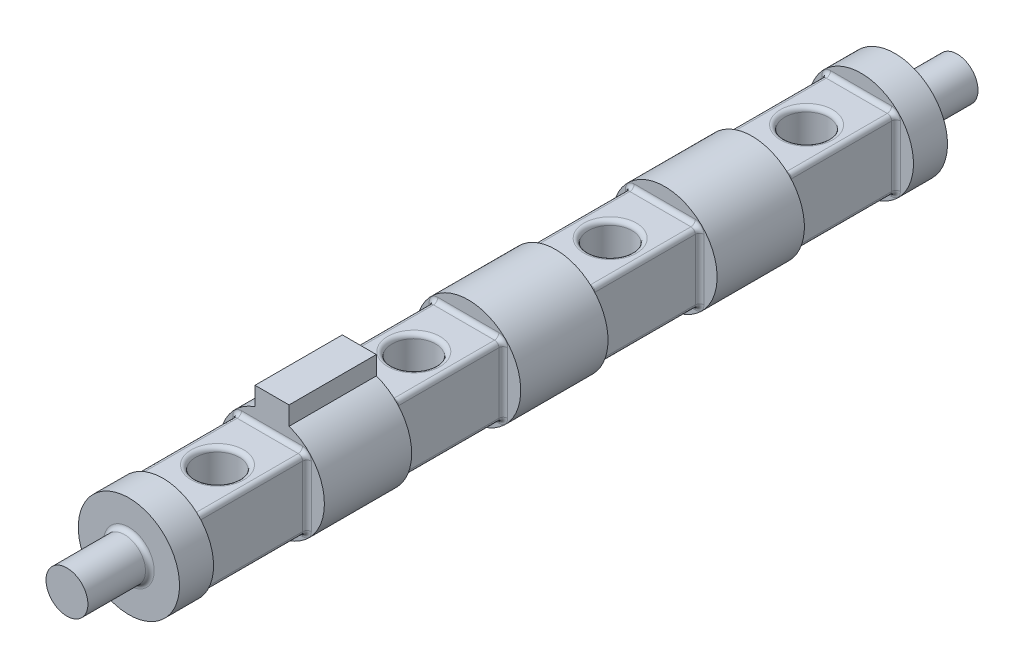
SolidWorks part; units mm, degrees
ref_plane "Front Plane" through (0, 0, 0) normal (0, 0, 1) x (1, 0, 0)
ref_plane "Top Plane" through (0, 0, 0) normal (0, 1, 0) x (1, 0, 0)
ref_plane "Right Plane" through (0, 0, 0) normal (1, 0, 0) x (0, 0, -1)
sketch "Sketch1" plane through (0, 0, 0) normal (0, 0, 1) x (1, 0, 0)
  circle A0 centre (0, 0) radius 6
  dimension "D3" = 12
extrude "Boss-Extrude1" add sketch "Sketch1" along normal blind 100
ref_plane "Midplane" through (0, 0, 50) normal (0, 0, -1) x (-1, 0, 0)
sketch "Sketch2" plane through (0, 0, 50) normal (0, 0, -1) x (-1, 0, 0)
  circle A2 centre (0, 0) radius 2.4
  dimension "D1" = 4.8
extrude "Boss-Extrude2" add sketch "Sketch2" along normal mid plane 102
sketch "Sketch3" plane through (0, 0, 0) normal (0, 0, -1) x (-1, 0, 0)
  line L1 (-4, -4) -> (4, -4)
  line L2 (-4, -4) -> (-4, 4)
  line L3 (-4, 4) -> (4, 4)
  line L4 (4, -4) -> (4, 4)
  line L5 (-4, -4) -> (4, 4) construction
  line L6 (-4, 4) -> (4, -4) construction
  circle A0 centre (0, 0) radius 6 construction
  circle A1 centre (0, 0) radius 6
  dimension "D1" = 8
  dimension "D2" = 8
extrude "Cut-Extrude1" cut sketch "Sketch3" against normal blind 12.5 from offset 10 offset against normal yes
sketch "Sketch5" plane through (0, 4, 0) normal (0, 1, 0) x (1, 0, 0)
  line L0 (0, 0) -> (0, -80.5016) construction
  line L3 (-4, -16.25) -> (4, -16.25) construction
  line L6 (-4, -22.5) -> (-4, -10) construction
  line L7 (4, -22.5) -> (4, -10) construction
  circle A0 centre (0, -16.25) radius 2.5
  dimension "D1" = 5
extrude "Cut-Extrude4" cut sketch "Sketch5" against normal through all
pattern_linear "LPattern1" count 4 spacing 22.5 along (0, 0, 1) of "Cut-Extrude1", "Cut-Extrude4"
sketch "Sketch10" plane through (0, 0, 0) normal (0, 0, -1) x (-1, 0, 0)
  circle A0 centre (0, 0) radius 6 construction
  circle A2 centre (0, 0) radius 2.4
  circle A3 centre (0, 0) radius 6
  circle A4 centre (0, 0) radius 2.4 construction
extrude "Cut-Extrude6" cut sketch "Sketch10" against normal blind 6.1
sketch "Sketch11" plane through (0, 0, 100) normal (0, 0, 1) x (1, 0, 0)
  circle A1 centre (0, 0) radius 2.4
  circle A3 centre (0, 0) radius 6
  circle A4 centre (0, 0) radius 6
  circle A5 centre (0, 0) radius 2.4
  dimension "D1" = 0
  dimension "D2" = 0
extrude "Cut-Extrude7" cut sketch "Sketch11" against normal blind 6.1
sketch "Sketch13" plane through (0, 0, 77.5) normal (0, 0, 1) x (1, 0, 0)
  circle A0 centre (0, 0) radius 5.8
  circle A1 centre (0, 0) radius 6 construction
  circle A2 centre (0, 0) radius 6
  dimension "D1" = 11.6
sketch "Sketch15" plane through (0, 0, 77.5) normal (0, 0, 1) x (1, 0, 0)
  line L0 (0, 0) -> (0, 5.8452) construction
  line L2 (-1.95, 0) -> (1.95, 0)
  line L3 (-1.95, 0) -> (-1.95, 7.8)
  line L4 (-1.95, 7.8) -> (1.95, 7.8)
  line L5 (1.95, 0) -> (1.95, 7.8)
  dimension "D1" = 7.8
  dimension "D2" = 3.9
extrude "Boss-Extrude4" add sketch "Sketch15" against normal up to surface (10 mm away) up to face at (0, 0, 67.5)
sketch "Sketch17" plane through (0, 0, 93.9) normal (0, 0, 1) x (1, 0, 0)
  circle A0 centre (0, 0) radius 6
  circle A1 centre (0, 0) radius 5.8
  circle A2 centre (0, 0) radius 6 construction
  dimension "D1" = 0.2
extrude "Cut-Extrude9" cut sketch "Sketch17" against normal up to surface (3.9 mm away) up to face at (0, 0, 90)
fillet "Fillet2" radius 0.5 42 edges at (-4, 0, 22.5) (-4, 0, 10) (-4, -4, 16.25) (0, -4, 22.5) (0, -4, 10) (0, -4, 13.75) (4, -4, 16.25) (4, 0, 22.5) (4, 0, 10) (4, 4, 16.25) (0, 4, 22.5) (-4, 4, 16.25) (0, 4, 10) (0, 4, 18.75) (0, 4, 45) (0, 4, 32.5) (0, 4, 41.25) (4, 0, 45) (4, 4, 38.75) (4, 0, 32.5) (0, -4, 45) (4, -4, 38.75) (0, -4, 32.5) (0, -4, 36.25) (-4, 4, 38.75) (-4, 0, 45) (-4, -4, 38.75) (-4, 0, 32.5) (-4, 0, 67.5) (-4, 0, 55) (-4, -4, 61.25) (0, -4, 67.5) (0, -4, 55) (0, -4, 58.75) (0, 4, 67.5) (-4, 4, 61.25) (0, 4, 55) (0, 4, 63.75) (4, -4, 61.25) (4, 0, 67.5) (4, 4, 61.25) (4, 0, 55)
fillet "Fillet3" radius 0.5 12 edges at (0, -4, 77.5) (0, -4, 81.25) (-4, -4, 83.75) (-4, 0, 77.5) (-4, 4, 83.75) (0, 4, 77.5) (0, 4, 86.25) (4, -4, 83.75) (4, 4, 83.75) (4, 0, 77.5) (-2.4, 0, 6.1) (2.4, 0, 93.9)
equation "\"T_length\"= 100"
equation "\"D1@Boss-Extrude1\"=\"T_length\""
equation "\"D1@Boss-Extrude2\"=\"T_length\"+2"
equation "\"linkage gap\"= 12.5"
equation "\"D1@Cut-Extrude1\"=\"linkage gap\""
equation "\"D3@LPattern1\"=\"linkage gap\"+\"linkage small gap\""
equation "\"linkage small gap\"= ( \"T_length\" - \"linkage gap\" * 4 ) / 5"
equation "\"D19@Cut-Extrude1\"=\"linkage small gap\""
